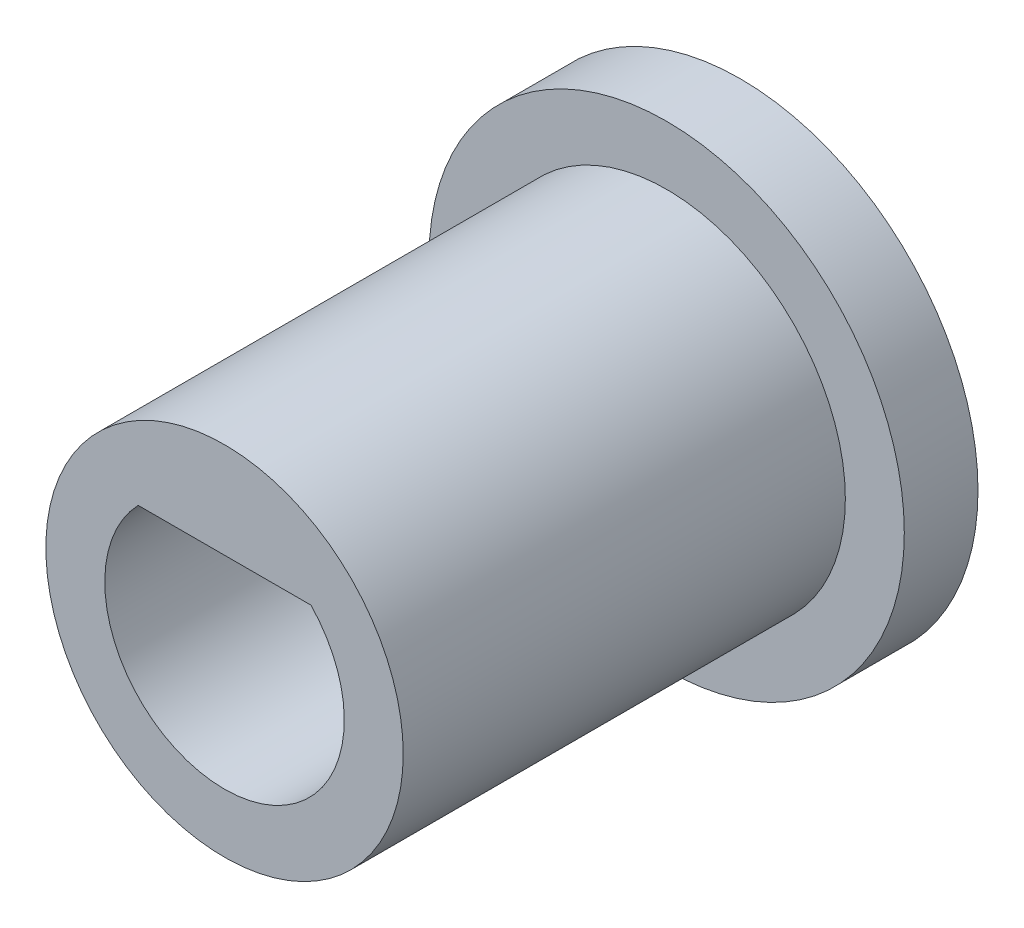
SolidWorks part; units mm, degrees
ref_plane "Front" through (0, 0, 0) normal (0, 0, 1) x (1, 0, 0)
ref_plane "Top" through (0, 0, 0) normal (0, 1, 0) x (1, 0, 0)
ref_plane "Right" through (0, 0, 0) normal (1, 0, 0) x (0, 0, -1)
sketch "Sketch1" plane through (0, 0, 0) normal (0, 0, 1) x (1, 0, 0)
  line L0 (-1.1726, 1.125) -> (1.1726, 1.125)
  circle A0 centre (0, 0) radius 2.425
  circle A1 centre (0, 0) radius 1.625
  circle A2 centre (0, 0) radius 3.225
  point P6 (0, -1.625)
  dimension "D2" = 3.25
  dimension "D3" = 2.75
  dimension "D1" = 0.8
  dimension "D4" = 1.6
extrude "Boss-Extrude1" add sketch "Sketch1" along normal blind 6 contours L0 A1 | A0 A1 region at (0, 1.3279, 0) region at (-2.3564, 0, 0)
extrude "Boss-Extrude2" add sketch "Sketch1<4>" against normal blind 1 contours A2 A0 | A0 A1 | L0 A1 region at (0, 1.3279, 0) region at (-2.3564, 0, 0) region at (-3.1338, 0, 0)
sketch "Sketch1<4>" plane through (0, 0, 0) normal (0, 0, 1) x (1, 0, 0) same geometry as "Sketch1"
equation "\"D3@Sketch1\"=\"axle_cut\"+\"axle_room\""
equation "\"axle_dia\"= 3"
equation "\"axle_cut\"= 2.5"
equation "\"axle_room\"= 0.25"
equation "\"print_thickness\"= 0.4"
equation "\"D4@Sketch1\"=\"print_thickness\"*4"
equation "\"D1@Sketch1\"=\"print_thickness\"*2"
equation "\"D2@Sketch1\"=\"axle_dia\"+\"axle_room\""
